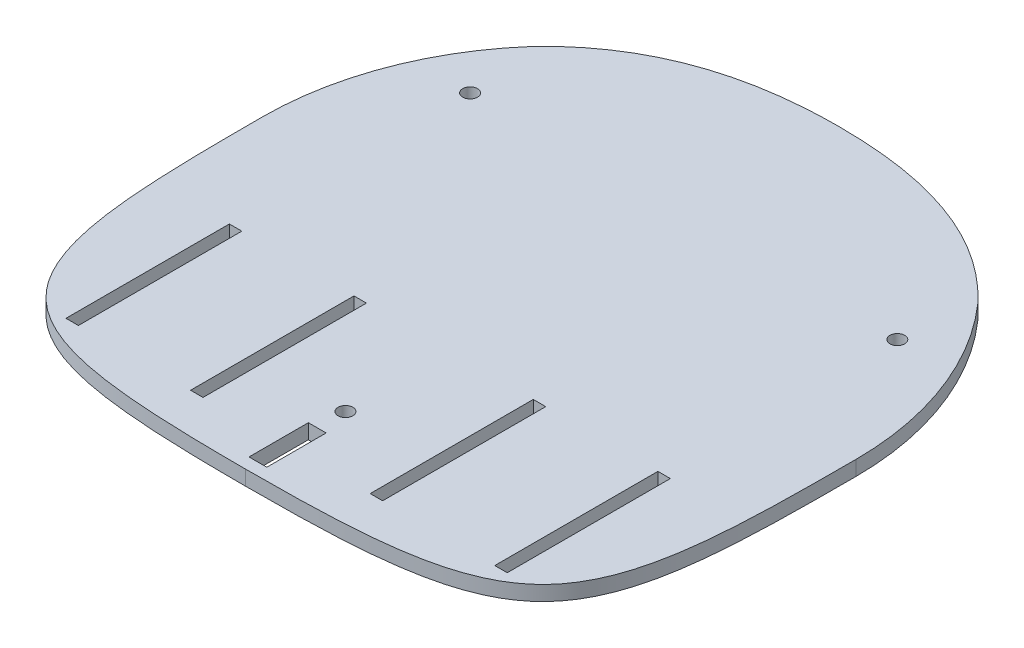
SolidWorks part; units mm, degrees
ref_plane "Front Plane" through (0, 0, 0) normal (0, 0, 1) x (1, 0, 0)
ref_plane "Top Plane" through (0, 0, 0) normal (0, 1, 0) x (1, 0, 0)
ref_plane "Right Plane" through (0, 0, 0) normal (1, 0, 0) x (0, 0, -1)
sketch "Layer1Limits" plane through (0, 0, 0) normal (0, 1, 0) x (1, 0, 0)
  line L0 (-127, 119.8228) -> (127, -134.1772) construction
  line L1 (-127, -134.1772) -> (127, -134.1772) construction
  line L2 (-127, -134.1772) -> (-127, 119.8228) construction
  line L3 (-127, 119.8228) -> (127, 119.8228) construction
  line L4 (127, -134.1772) -> (127, 119.8228) construction
  line L5 (127, 119.8228) -> (-127, -134.1772) construction
  line L6 (0, -1000) -> (0, 49000) construction
  point P4 (0, -7.1772)
  dimension "D1" = 254
  dimension "D2" = 254
sketch "Sketch1" plane through (0, 0, 0) normal (0, 1, 0) x (1, 0, 0)
  line L0 (0, 0) -> (-157.9039, -157.9039) construction
  line L1 (0, -134.1772) -> (0, 127) construction
  line L2 (-127, -134.1772) -> (127, -134.1772) construction
  arc A0 (127, 0) -> (-127, 0) centre (0, 0) ccw
  spline S0 degree 3 poles (-127, 0) (-127, -50.6247) (-125.8471, -127.4032) (-59.0891, -134.1772) (0, -134.1772) knots 0 0 0 0 0.496988 1 1 1 1
  spline S1 degree 3 poles (127, 0) (127, -50.6247) (125.8471, -127.4032) (59.0891, -134.1772) (0, -134.1772) knots 0 0 0 0 0.496988 1 1 1 1
  dimension "D1" = 254
extrude "Base" add sketch "Sketch1" along normal blind 6.35
sketch "Sketch16" plane through (0, 6.35, 0) normal (0, 1, 0) x (1, 0, 0)
  line L0 (0, -1000) -> (0, 49000) construction
  line L1 (-95.2696, 133.35) -> (-95.2696, 83.9803)
  line L2 (-95.2696, 133.35) -> (95.2696, 133.35)
  line L3 (95.2696, 133.35) -> (95.2696, 83.9803)
  arc A0 (127, 0) -> (-127, 0) centre (0, 0) ccw construction
  spline S0 degree 3 poles (-95.2696, 83.9803) (-69.156, 111.7112) (-34.9729, 119.8228) (0, 119.8228) knots 0 0 0 0 1 1 1 1
  spline S1 degree 3 poles (95.2696, 83.9803) (69.156, 111.7112) (34.9729, 119.8228) (0, 119.8228) knots 0 0 0 0 1 1 1 1
extrude "EmptySpaceTrim" cut sketch "Sketch16" against normal through all
sketch "ShaftLayout" plane through (0, 6.35, 0) normal (0, 1, 0) x (1, 0, 0)
  line L0 (-127, 0) -> (127, 0) construction
  line L1 (0, 133.35) -> (0, -127) construction
  line L2 (-114.7053, -6.35) -> (-104.7993, -6.35)
  line L3 (-36.3853, -38) -> (-94.3853, -38)
  line L4 (-36.3853, -38) -> (-36.3853, 38)
  line L5 (-36.3853, 38) -> (-94.3853, 38)
  line L6 (-94.3853, -38) -> (-94.3853, 38)
  line L7 (-36.3853, -38) -> (-94.3853, 38) construction
  line L8 (-36.3853, 38) -> (-94.3853, -38) construction
  line L9 (-102.0053, -15.875) -> (-104.7993, -15.875)
  line L10 (-102.0053, -15.875) -> (-102.0053, 15.875)
  line L11 (-102.0053, 15.875) -> (-104.7993, 15.875)
  line L12 (-104.7993, -15.875) -> (-104.7993, 15.875)
  line L13 (-102.0053, -15.875) -> (-104.7993, 15.875) construction
  line L14 (-102.0053, 15.875) -> (-104.7993, -15.875) construction
  line L15 (-114.7053, -6.35) -> (-114.7053, 6.35)
  line L16 (-104.7993, -6.35) -> (-104.7993, 6.35)
  line L17 (-114.7053, 6.35) -> (-104.7993, 6.35)
  line L18 (-114.7053, -6.35) -> (-104.7993, 6.35) construction
  line L19 (-104.7993, -6.35) -> (-114.7053, 6.35) construction
  line L20 (-116.2928, -9.525) -> (-114.7053, -9.525)
  line L21 (-116.2928, -9.525) -> (-116.2928, 9.525)
  line L22 (-114.7053, -9.525) -> (-114.7053, 9.525)
  line L23 (-116.2928, 9.525) -> (-114.7053, 9.525)
  line L24 (-116.2928, -9.525) -> (-114.7053, 9.525) construction
  line L25 (-114.7053, -9.525) -> (-116.2928, 9.525) construction
  line L26 (-127.4053, -7.9375) -> (-116.2928, -7.9375)
  line L27 (-127.4053, -7.9375) -> (-127.4053, 7.9375)
  line L28 (-116.2928, -7.9375) -> (-116.2928, 7.9375)
  line L29 (-127.4053, 7.9375) -> (-116.2928, 7.9375)
  line L30 (-127.4053, -7.9375) -> (-116.2928, 7.9375) construction
  line L31 (-116.2928, -7.9375) -> (-127.4053, 7.9375) construction
  line L32 (-17.3353, -7.9375) -> (-28.4478, -7.9375)
  line L33 (-30.0353, -9.525) -> (-28.4478, -9.525)
  line L34 (-30.0353, -9.525) -> (-30.0353, 9.525)
  line L35 (-30.0353, 9.525) -> (-28.4478, 9.525)
  line L36 (-28.4478, -9.525) -> (-28.4478, 9.525)
  line L37 (-30.0353, -9.525) -> (-28.4478, 9.525) construction
  line L38 (-30.0353, 9.525) -> (-28.4478, -9.525) construction
  line L39 (-17.3353, -7.9375) -> (-17.3353, 7.9375)
  line L40 (-28.4478, -7.9375) -> (-28.4478, 7.9375)
  line L41 (-17.3353, 7.9375) -> (-28.4478, 7.9375)
  line L42 (-17.3353, -7.9375) -> (-28.4478, 7.9375) construction
  line L43 (-28.4478, -7.9375) -> (-17.3353, 7.9375) construction
  line L45 (-67.3853, -10.033) -> (-56.3853, -10.033)
  line L46 (-67.3853, -10.033) -> (-67.3853, 10.033)
  line L47 (-67.3853, 10.033) -> (-56.3853, 10.033)
  line L48 (-56.3853, -10.033) -> (-56.3853, 10.033)
  line L49 (-67.3853, -10.033) -> (-56.3853, 10.033) construction
  line L50 (-67.3853, 10.033) -> (-56.3853, -10.033) construction
  point P10 (-65.3853, 0)
  point P15 (-103.4023, 0)
  point P20 (-29.2416, 0)
  point P21 (-109.7523, 0)
  point P22 (-115.4991, 0)
  point P23 (-121.8491, 0)
  point P40 (-61.8853, 0)
  point P41 (-22.8916, 0)
  point P50 (0, 0)
  dimension "D1" = 58
  dimension "D2" = 76
  dimension "D3" = 7.62
  dimension "D4" = 2.794
  dimension "D5" = 31.75
  dimension "D6" = 9.906
  dimension "D7" = 12.7
  dimension "D8" = 19.05
  dimension "D9" = 1.5875
  dimension "D10" = 12.7
  dimension "D11" = 15.875
  dimension "D12" = 19.05
  dimension "D13" = 1.5875
  dimension "D14" = 15.875
  dimension "D15" = 12.7
  dimension "D16" = 6.35
  dimension "D17" = 20.066
  dimension "D18" = 20
  dimension "D19" = 11
sketch "MotorLayout" plane through (0, 6.35, 0) normal (0, 1, 0) x (1, 0, 0)
  line L0 (-94.3853, -81.74) -> (-114.3853, -81.74) construction
  line L1 (-94.3853, -110.24) -> (-18.3853, -110.24)
  line L2 (-94.3853, -110.24) -> (-94.3853, -53.24)
  line L3 (-94.3853, -53.24) -> (-18.3853, -53.24)
  line L4 (-18.3853, -110.24) -> (-18.3853, -53.24)
  line L5 (-94.3853, -110.24) -> (-18.3853, -53.24) construction
  line L6 (-94.3853, -53.24) -> (-18.3853, -110.24) construction
  line L7 (-114.7053, -92.0587) -> (-104.7993, -92.0587)
  line L8 (-104.7993, -97.615) -> (-102.0053, -97.615)
  line L9 (-104.7993, -97.615) -> (-104.7993, -65.865)
  line L10 (-104.7993, -65.865) -> (-102.0053, -65.865)
  line L11 (-102.0053, -97.615) -> (-102.0053, -65.865)
  line L12 (-104.7993, -97.615) -> (-102.0053, -65.865) construction
  line L13 (-104.7993, -65.865) -> (-102.0053, -97.615) construction
  line L14 (-36.3853, -38) -> (-94.3853, -38) construction
  line L15 (-114.7053, -92.0587) -> (-114.7053, -71.4212)
  line L16 (-104.7993, -92.0587) -> (-104.7993, -71.4212)
  line L17 (-114.7053, -71.4212) -> (-104.7993, -71.4212)
  line L18 (-114.7053, -92.0587) -> (-104.7993, -71.4212) construction
  line L19 (-104.7993, -92.0587) -> (-114.7053, -71.4212) construction
  line L20 (-103.4023, -1000) -> (-103.4023, 49000) construction
  line L21 (-34.8953, -53.24) -> (-34.8953, -110.24) construction
  point P0 (-56.3853, -81.74)
  point P7 (-103.4023, -81.74)
  point P14 (-109.7523, -81.74)
  dimension "D1" = 20
  dimension "D2" = 76
  dimension "D3" = 57
  dimension "D4" = 2.794
  dimension "D5" = 15.24
  dimension "D6" = 31.75
  dimension "D7" = 20.6375
  dimension "D8" = 12.7
  dimension "D9" = 7.62
  dimension "D10" = 16.51
sketch "Sketch8" plane through (0, 6.35, 0) normal (0, 1, 0) x (1, 0, 0)
  line L0 (-94.3853, -81.74) -> (-18.3853, -81.74) construction
  line L1 (-18.3853, -110.24) -> (-18.3853, -53.24) construction
  line L2 (-94.3853, -53.24) -> (-18.3853, -53.24) construction
  line L3 (-35.7113, -116.717) -> (-41.0453, -116.717)
  line L4 (-35.7113, -116.717) -> (-35.7113, -46.763)
  line L5 (-35.7113, -46.763) -> (-41.0453, -46.763)
  line L6 (-41.0453, -116.717) -> (-41.0453, -46.763)
  line L7 (-35.7113, -116.717) -> (-41.0453, -46.763) construction
  line L8 (-35.7113, -46.763) -> (-41.0453, -116.717) construction
  line L9 (0, -1000) -> (0, 49000) construction
  line L10 (-94.3853, -110.24) -> (-18.3853, -110.24) construction
  line L11 (-3.81, -128.9302) -> (3.81, -128.9302)
  line L12 (89.0513, -46.763) -> (94.3853, -116.59) construction
  line L13 (89.0513, -116.59) -> (94.3853, -46.763) construction
  line L14 (35.7113, -46.763) -> (41.0453, -116.59) construction
  line L15 (-89.0513, -116.717) -> (-94.3853, -116.717)
  line L16 (-89.0513, -116.717) -> (-89.0513, -46.763)
  line L17 (-89.0513, -46.763) -> (-94.3853, -46.763)
  line L18 (-94.3853, -116.717) -> (-94.3853, -46.763)
  line L19 (-89.0513, -116.717) -> (-94.3853, -46.763) construction
  line L20 (-89.0513, -46.763) -> (-94.3853, -116.717) construction
  line L21 (-94.3853, -110.24) -> (-94.3853, -53.24) construction
  line L22 (-3.81, -128.9302) -> (-3.81, -103.5302)
  line L23 (35.7113, -116.59) -> (41.0453, -46.763) construction
  line L24 (-3.81, -103.5302) -> (3.81, -103.5302)
  line L25 (3.81, -128.9302) -> (3.81, -103.5302)
  line L26 (-3.81, -128.9302) -> (3.81, -103.5302) construction
  line L27 (-3.81, -103.5302) -> (3.81, -128.9302) construction
  line L29 (94.3853, -116.59) -> (94.3853, -46.763)
  line L30 (89.0513, -46.763) -> (94.3853, -46.763)
  line L31 (89.0513, -116.59) -> (89.0513, -46.763)
  line L32 (89.0513, -116.59) -> (94.3853, -116.59)
  line L33 (41.0453, -116.59) -> (41.0453, -46.763)
  line L34 (35.7113, -46.763) -> (41.0453, -46.763)
  line L35 (35.7113, -116.59) -> (35.7113, -46.763)
  line L36 (35.7113, -116.59) -> (41.0453, -116.59)
  point P6 (-63.7079, -81.74)
  point P7 (-38.2513, -81.74)
  point P16 (0, -116.2302)
  point P19 (-91.5913, -81.74)
  point P39 (91.5913, -81.74)
  point P40 (38.2513, -81.74)
  dimension "D1" = 5.334
  dimension "D2" = 6.477
  dimension "D4" = 7.62
  dimension "D5" = 25.4
  dimension "D6" = 6.477
  dimension "D3" = 2
extrude "MotorCut" cut sketch "Sketch8" against normal through all
sketch "Sketch11" plane through (0, 6.35, 0) normal (0, 1, 0) x (1, 0, 0)
  line L0 (0, -1000) -> (0, 49000) construction
  line L1 (-127, 0) -> (127, 0) construction
  circle A1 centre (0, -91.44) radius 3.175
  circle A2 centre (-91.44, 53.34) radius 3.175
  circle A3 centre (91.44, 53.34) radius 3.175
  dimension "D1" = 6.35
  dimension "D2" = 91.44
  dimension "D3" = 6.35
  dimension "D6" = 91.44
  dimension "D4" = 53.34
extrude "ScrewCut" cut sketch "Sketch11" against normal through all
